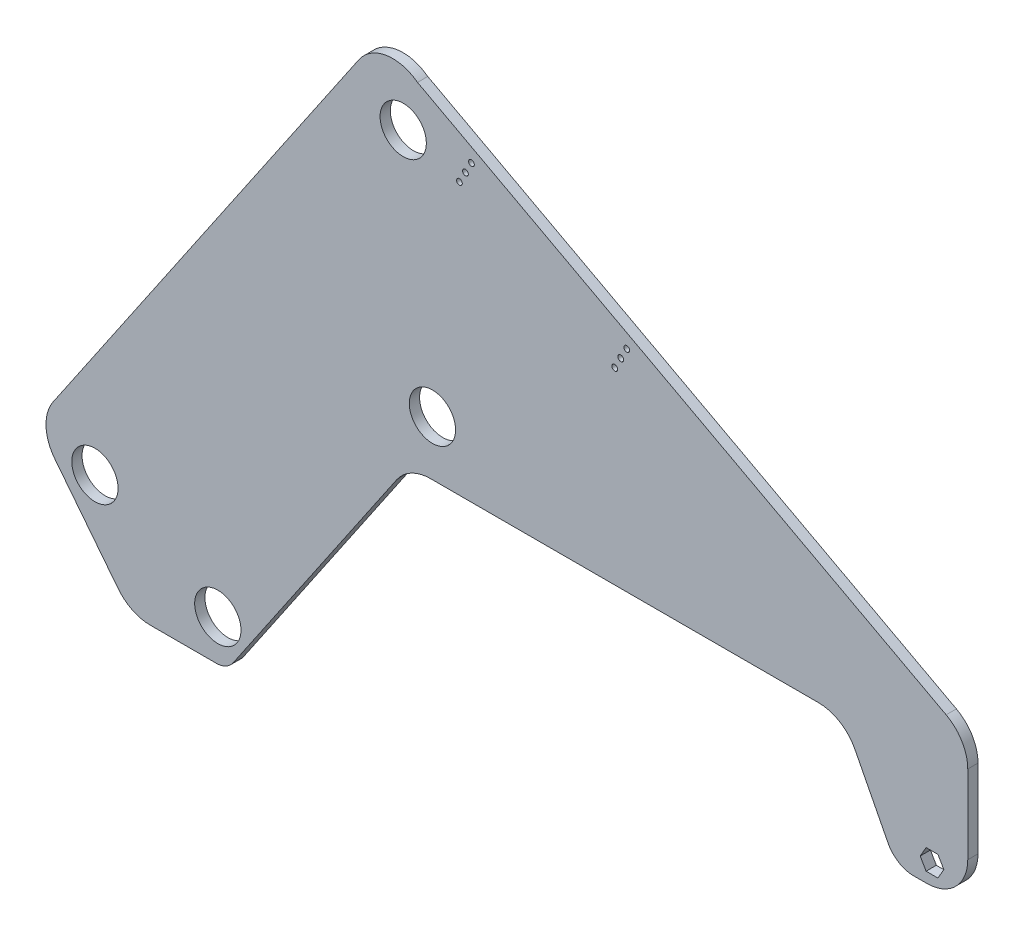
SolidWorks part; units mm, degrees
other "Markup1"
sketch "Sketch1" plane through (-441.7893, 331.8239, 6.35) normal (-0.0431, 0.0102, 0.999) x (0.9985, 0.0354, 0.0427)
sketch "Sketch2" plane through (-413.6701, 343.933, 6.35) normal (-0.0431, 0.0102, 0.999) x (0.9985, 0.0354, 0.0427)
sketch "Sketch3" plane through (-436.3774, 318.5567, 6.35) normal (-0.0431, 0.0102, 0.999) x (0.9985, 0.0354, 0.0427)
sketch "Sketch5" plane through (-436.3774, 318.5567, 6.35) normal (-0.0431, 0.0102, 0.999) x (0.9985, 0.0354, 0.0427)
sketch "Sketch7" plane through (-430.3226, 318.5567, 6.35) normal (-0.0431, 0.0102, 0.999) x (0.9985, 0.0354, 0.0427)
sketch "Sketch9" plane through (-430.3226, 318.5567, 6.35) normal (-0.0431, 0.0102, 0.999) x (0.9985, 0.0354, 0.0427)
sketch "Sketch11" plane through (-430.3226, 318.5567, 6.35) normal (-0.0431, 0.0102, 0.999) x (0.9985, 0.0354, 0.0427)
sketch "Sketch13" plane through (-430.3226, 318.5567, 6.35) normal (-0.0431, 0.0102, 0.999) x (0.9985, 0.0354, 0.0427)
sketch "Sketch15" plane through (-430.3226, 318.5567, 6.35) normal (-0.0431, 0.0102, 0.999) x (0.9985, 0.0354, 0.0427)
other "Markup2"
sketch "Sketch4" plane through (102.4721, 318.5567, 6.35) normal (0.9364, 0.1073, 0.3342) x (0.3416, -0.0598, -0.9379)
sketch "Sketch6" plane through (102.4721, 318.5567, 6.35) normal (0.9364, 0.1073, 0.3342) x (0.3416, -0.0598, -0.9379)
sketch "Sketch8" plane through (141.2086, 318.5567, 6.35) normal (0.9364, 0.1073, 0.3342) x (0.3416, -0.0598, -0.9379)
sketch "Sketch10" plane through (141.2086, 318.5567, 6.35) normal (0.9364, 0.1073, 0.3342) x (0.3416, -0.0598, -0.9379)
sketch "Sketch12" plane through (141.2086, 318.5567, 6.35) normal (0.9364, 0.1073, 0.3342) x (0.3416, -0.0598, -0.9379)
sketch "Sketch14" plane through (141.2086, 318.5567, 6.35) normal (0.9364, 0.1073, 0.3342) x (0.3416, -0.0598, -0.9379)
sketch "Sketch16" plane through (141.2086, 318.5567, 6.35) normal (0.9364, 0.1073, 0.3342) x (0.3416, -0.0598, -0.9379)
material "Lexan"
ref_plane "Front Plane" through (0, 0, 0) normal (0, 0, 1) x (1, 0, 0)
ref_plane "Top Plane" through (0, 0, 0) normal (0, 1, 0) x (1, 0, 0)
ref_plane "Right Plane" through (0, 0, 0) normal (1, 0, 0) x (0, 0, -1)
sketch "Model" plane through (0, 0, 0) normal (0, 0, 1) x (1, 0, 0)
  line L1 (-191.9011, 104.6502) -> (-112.96, 104.6502)
  line L3 (-314.2383, -55.3595) -> (-212.8994, 93.5413)
  line L4 (-236.3032, 307.4477) -> (-425.9209, 28.8361)
  line L5 (-424.8981, -1.1437) -> (-385.5815, -51.2028)
  line L13 (126.3831, 53.8502) -> (122.717, 60.2002)
  line L14 (122.717, 60.2002) -> (115.3846, 60.2002)
  line L15 (115.3846, 60.2002) -> (111.7185, 53.8502)
  line L16 (111.7185, 53.8502) -> (115.3846, 47.5002)
  line L17 (115.3846, 47.5002) -> (122.717, 47.5002)
  line L18 (122.717, 47.5002) -> (126.3831, 53.8502)
  line L19 (-365.606, -60.914) -> (-324.7375, -60.914)
  line L20 (-871.0211, -88.854) -> (370.1019, -88.854) construction
  line L22 (141.2086, 66.5502) -> (141.2086, 78.8846)
  line L27 (107.6196, 41.1502) -> (115.8086, 41.1502)
  line L28 (-399.9752, 2.586) -> (-323.7752, -35.514) construction
  line L29 (-323.7752, -35.514) -> (-190.7071, 138.5169) construction
  line L30 (-190.7071, 138.5169) -> (-208.8329, 283.4378) construction
  line L31 (-208.8329, 283.4378) -> (-399.9752, 2.586) construction
  line L32 (91.8004, 50.8135) -> (71.26, 90.8456)
  line L33 (48.6612, 104.6502) -> (-11.3966, 104.6502)
  line L34 (141.2086, 78.8846) -> (141.2086, 115.3033)
  line L35 (127.8091, 137.6897) -> (-86.3327, 252.4836)
  line L36 (-112.96, 104.6502) -> (-68.51, 104.6502)
  line L37 (-122.3008, 271.7648) -> (-85.2777, 251.9181)
  line L38 (-199.9496, 313.3896) -> (-69.3866, 236.7709)
  line L39 (-69.3866, 236.7709) -> (-66.6265, 241.9198)
  line L40 (-68.51, 104.6502) -> (-2.1388, 104.6502)
  line L41 (-122.3008, 271.7648) -> (-199.9496, 313.3896)
  line L42 (-73.4763, 229.1419) -> (-69.3866, 236.7709)
  line L43 (-70.2266, 235.2039) -> (-73.9468, 228.2641) construction
  line L44 (-199.9496, 313.3896) -> (-165.6808, 288.3909)
  line L45 (-165.6808, 288.3909) -> (-162.9207, 293.5397)
  line L46 (-165.6808, 288.3909) -> (-168.0579, 283.9566)
  line L47 (-166.5208, 286.8238) -> (-170.241, 279.8841) construction
  arc A3 (121.2475, 59.8082) -> (121.352, 60.2002) centre (96.7586, 66.5502) ccw
  circle A9 centre (-323.7752, -35.514) radius 14.351
  circle A10 centre (-399.9752, 2.586) radius 14.351
  circle A12 centre (-190.7071, 138.5169) radius 14.351
  arc A15 (107.6196, 41.1502) -> (91.8004, 50.8135) centre (107.6196, 58.9302) cw
  arc A21 (-191.9011, 104.6502) -> (-212.8994, 93.5413) centre (-191.9011, 79.2502) ccw
  circle A22 centre (-208.8329, 283.4378) radius 14.351
  circle A24 centre (119.0508, 53.8502) radius 6.35 construction
  arc A31 (-324.7375, -60.914) -> (-314.2383, -55.3595) centre (-324.7375, -48.214) ccw
  arc A40 (114.7422, 48.6129) -> (115.0458, 48.9225) centre (96.7586, 66.5502) ccw
  arc A43 (115.8086, 41.1502) -> (141.2086, 66.5502) centre (115.8086, 66.5502) ccw
  arc A44 (-236.3032, 307.4477) -> (-199.9496, 313.3896) centre (-215.305, 293.1567) cw
  arc A45 (-365.606, -60.914) -> (-385.5815, -51.2028) centre (-365.606, -35.514) cw
  arc A46 (71.26, 90.8456) -> (48.6612, 104.6502) centre (48.6612, 79.2502) ccw
  arc A47 (141.2086, 115.3033) -> (127.8091, 137.6897) centre (115.8086, 115.3033) ccw
  arc A48 (-424.8981, -1.1437) -> (-425.9209, 28.8361) centre (-404.9226, 14.5451) cw
  circle A50 centre (-70.2266, 235.2039) radius 1.778
  circle A51 centre (-73.9468, 228.2641) radius 1.778
  circle A52 centre (-77.667, 221.3244) radius 1.778
  circle A53 centre (-166.5208, 286.8238) radius 1.778
  circle A54 centre (-170.241, 279.8841) radius 1.778
  circle A55 centre (-173.9612, 272.9443) radius 1.778
  ellipse E0 centre (-551.1692, 173.9527) end of major axis (-591.2054, 216.0961) minor radius 17.278
  point P31 (-177.5612, 330.9695)
  point P34 (100.2935, -12.8222)
  point P43 (-377.9543, -60.914)
  point P55 (96.7586, 41.1502)
  point P59 (174.831, 53.8502)
  point P60 (-205.3388, 104.6502)
  point P64 (-436.3774, 13.472)
  dimension "D3" = 38.1
  dimension "D4" = 104.6502
  dimension "D5" = 76.2
  dimension "D6" = 44.45
  dimension "D7" = 12.7
  dimension "D8" = 28.702
  dimension "D11" = 139.7
  dimension "D12" = 27.94
  dimension "D21" = 124.238
  dimension "D13" = 12.7
  dimension "D16" = 355.6
  dimension "D23" = 25.4
  dimension "D24" = 25.4
  dimension "D26" = 25.4
  dimension "D14" = 406.4
  dimension "D20" = 254
  dimension "D29" = 25.4
  dimension "D31" = 25.4
  dimension "D25" = 88.9
  dimension "D30" = 17.78
  dimension "D32" = 25.4
  dimension "D33" = 25.4
  dimension "D34" = 151.384
  dimension "D35" = 5.842
  dimension "D37" = 3
  dimension "D38" = 7.874
  dimension "D36" = 3.556
  dimension "D41" = 3.556
  dimension "D9" = 19.05
  dimension "D10" = 146.05
  dimension "D15" = 33.8667
  dimension "D17" = 339.725
  dimension "D18" = 219.075
  dimension "D19" = 50.8
  dimension "D22" = 25.4
  dimension "D27" = 53.2168
  dimension "D28" = 12.7
  dimension "D39" = 5.842
  dimension "D40" = 42.418
  dimension "D43" = 7.874
  dimension "D42" = 3
extrude "Boss-Extrude1" add sketch "Model" along normal blind 6.35 contours A51 A50 L38 A44 L4 A48 L5 A45 L19 A31 L3 A21 L1 L36 L40 L33 A46 L32 A15 L27 A43 L22 L34 A47 L35 L39 A52 A22 A12 A10 A9 L18 L17 L16 L15 L14 L13 | L37 L41 L38 L39 L35 | L44 L45 L38 | L38 L45 L41 region at (-206.9871, 107.7659, 0) region at (-175.5192, 299.6797, 0) region at (-176.4392, 297.9634, 0) region at (-106.6772, 261.0467, 0)
